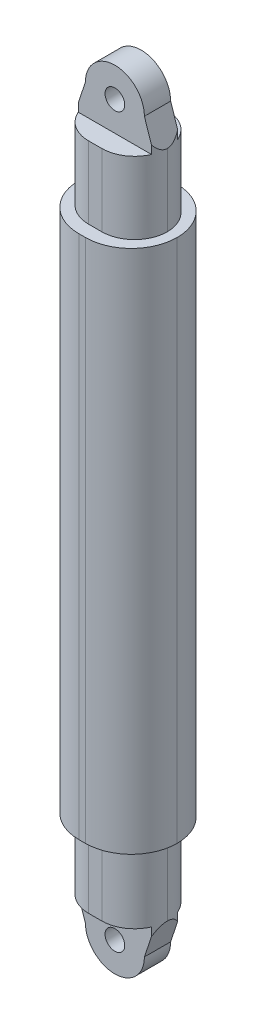
SolidWorks part; units mm, degrees
ref_plane "Front Plane" through (0, 0, 0) normal (0, 0, 1) x (1, 0, 0)
ref_plane "Top Plane" through (0, 0, 0) normal (0, 1, 0) x (1, 0, 0)
ref_plane "Right Plane" through (0, 0, 0) normal (1, 0, 0) x (0, 0, -1)
sketch "Sketch2" plane through (0, 0, 0) normal (0, 0, 1) x (1, 0, 0)
  line L1 (-6, -60) -> (6, -60)
  line L2 (-6, -60) -> (-6, 60)
  line L3 (-6, 60) -> (6, 60)
  line L4 (6, -60) -> (6, 60)
  line L5 (-6, -60) -> (6, 60) construction
  line L6 (-6, 60) -> (6, -60) construction
  point P0 (0, 0)
  dimension "D1" = 120
extrude "Boss-Extrude1" add sketch "Sketch2" along normal blind 10
fillet "Fillet1" radius 5 4 edges at (-6, 0, 0) (6, 0, 0) (6, 0, 10) (-6, 0, 10)
sketch "Sketch3" plane through (0, 0, 0) normal (0, 0, 1) x (1, 0, 0)
  line L0 (-6, -60) -> (-6, 60) construction
  line L1 (6, -60) -> (-6, -60)
  line L2 (6, -60) -> (6, -51)
  line L3 (6, -51) -> (-6, -51)
  line L4 (-6, -60) -> (-6, -51)
  line L6 (-6, -51) -> (-4.5, -55.5)
  line L7 (6, -51) -> (4.5, -55.5)
  arc A0 (-4.5, -55.5) -> (4.5, -55.5) centre (0, -55.5) ccw
  dimension "D1" = 4.5
  dimension "D2" = 9
extrude "Cut-Extrude1" cut sketch "Sketch3" along normal blind 3 contours L6 A0 L7 L3 | A0 L1 L2 L7 | A0 L6 L4 L1 region at (4.7812, -57.2492, 0) region at (-4.7812, -57.2492, 0) region at (0, -54.8597, 0)
extrude "Cut-Extrude2" cut sketch "Sketch3<2>" along normal blind 3 from offset 7 contours L2 L3 L4 L1
sketch "Sketch3<2>" plane through (0, 0, 0) normal (0, 0, 1) x (1, 0, 0) same geometry as "Sketch3"
mirror "Mirror1" about plane through (0, 0, 0) normal (0, 1, 0) of "Cut-Extrude2", "Cut-Extrude1"
extrude "Cut-Extrude4" cut sketch "Sketch3<4>" against normal blind 4 and the other way through all contours A0 L1 L2 L7 | A0 L6 L4 L1 region at (4.7812, -57.2492, 0) region at (-4.7812, -57.2492, 0)
sketch "Sketch3<4>" plane through (0, 0, 0) normal (0, 0, 1) x (1, 0, 0) same geometry as "Sketch3"
sketch "Sketch7" plane through (0, 0, 3) normal (0, 0, -1) x (-1, 0, 0)
  circle A0 centre (0, -55.5) radius 1.5
  dimension "D1" = 3
extrude "Cut-Extrude5" cut sketch "Sketch7" against normal through all
mirror "Mirror3" about plane through (0, 0, 0) normal (0, 1, 0) of "Cut-Extrude5"
mirror "Mirror4" about plane through (0, 0, 0) normal (0, 1, 0) of "Cut-Extrude4"
ref_plane "Plane1" through (0, 0, 5) normal (0, 0, 1) x (1, 0, 0)
sketch "Sketch9" plane through (0, 0, 5) normal (0, 0, 1) x (1, 0, 0)
  line L0 (-7.5, -40) -> (7.5, -40)
  line L1 (-7.5, -40) -> (-7.5, 40)
  line L2 (-7.5, 40) -> (7.5, 40)
  line L3 (7.5, -40) -> (7.5, 40)
  line L4 (-7.5, -40) -> (7.5, 40) construction
  line L5 (-7.5, 40) -> (7.5, -40) construction
  line L6 (0, 40) -> (0, -40) construction
  point P0 (0, 0)
  dimension "D1" = 80
  dimension "D2" = 15
extrude "Boss-Extrude2" add sketch "Sketch9" along normal blind 7 and the other way blind 7
fillet "Fillet3" radius 7 4 edges at (-7.5, 0, 12) (7.5, 0, 12) (7.5, 0, -2) (-7.5, 0, -2)
